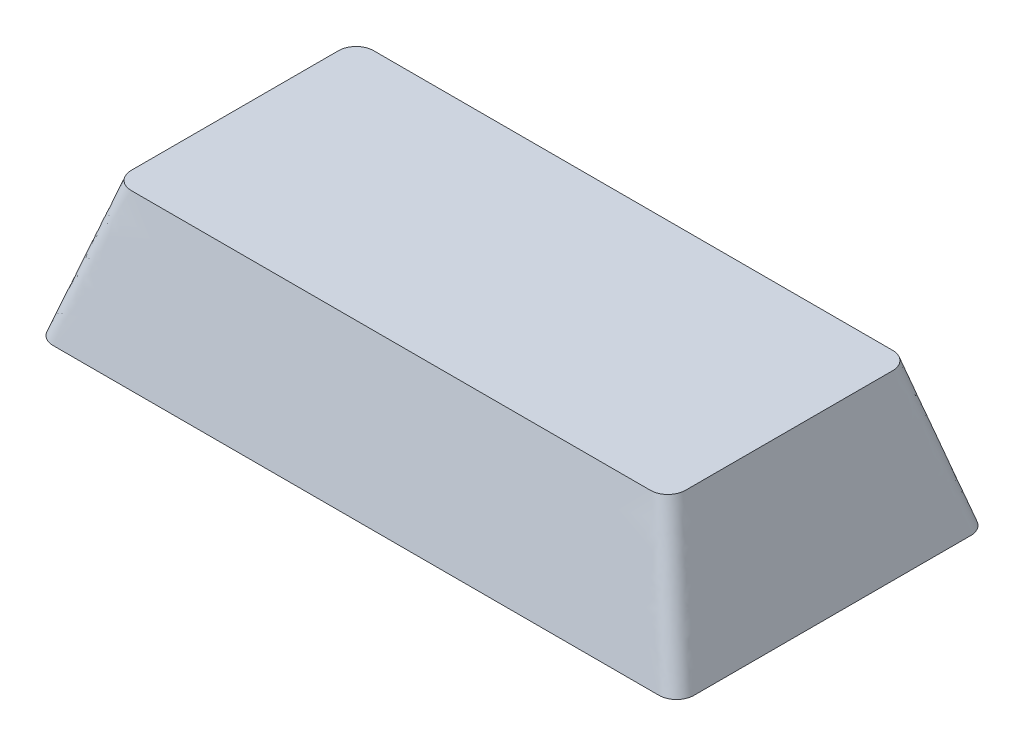
SolidWorks part; units mm, degrees
ref_plane "Alzado" through (0, 0, 0) normal (0, 0, 1) x (1, 0, 0)
ref_plane "Planta" through (0, 0, 0) normal (0, 1, 0) x (1, 0, 0)
ref_plane "Vista lateral" through (0, 0, 0) normal (1, 0, 0) x (0, 0, -1)
sketch "Croquis2" plane through (0, 0, 0) normal (0, 1, 0) x (1, 0, 0)
  line L1 (-17.4879, -9.0043) -> (17.4879, -9.0043)
  line L2 (-18.5039, -7.9883) -> (-18.5039, 7.9883)
  line L3 (-17.4879, 9.0043) -> (17.4879, 9.0043)
  line L4 (18.5039, -7.9883) -> (18.5039, 7.9883)
  arc A0 (-18.5039, 7.9883) -> (-17.4879, 9.0043) centre (-17.4879, 7.9883) cw
  arc A1 (-17.4879, -9.0043) -> (-18.5039, -7.9883) centre (-17.4879, -7.9883) cw
  arc A2 (17.4879, -9.0043) -> (18.5039, -7.9883) centre (17.4879, -7.9883) ccw
  arc A3 (17.4879, 9.0043) -> (18.5039, 7.9883) centre (17.4879, 7.9883) cw
  point P4 (18.5039, 0)
  point P6 (0, 9.0043)
  dimension "D3" = 1.016
  dimension "D1" = 37.0078
  dimension "D2" = 18.0086
ref_plane "Plano1" through (0, 8.001, 0) normal (0, 1, 0) x (1, 0, 0)
sketch "Croquis3" plane through (0, 8.001, 0) normal (0, 1, 0) x (1, 0, 0)
  line L1 (-14.986, -6.9977) -> (14.986, -6.9977)
  line L2 (-16.002, -5.9817) -> (-16.002, 5.9817)
  line L3 (-14.986, 6.9977) -> (14.986, 6.9977)
  line L4 (16.002, -5.9817) -> (16.002, 5.9817)
  line L5 (-16.002, -6.9977) -> (16.002, 6.9977) construction
  line L6 (-16.002, 6.9977) -> (16.002, -6.9977) construction
  arc A0 (14.986, 6.9977) -> (16.002, 5.9817) centre (14.986, 5.9817) cw
  arc A1 (14.986, -6.9977) -> (16.002, -5.9817) centre (14.986, -5.9817) ccw
  arc A2 (-14.986, -6.9977) -> (-16.002, -5.9817) centre (-14.986, -5.9817) cw
  arc A3 (-16.002, 5.9817) -> (-14.986, 6.9977) centre (-14.986, 5.9817) cw
  point P0 (0, 0)
  dimension "D3" = 1.016
  dimension "D1" = 32.004
  dimension "D2" = 13.9954
loft "Recubrir1" add profiles "Croquis3", "Croquis2"
